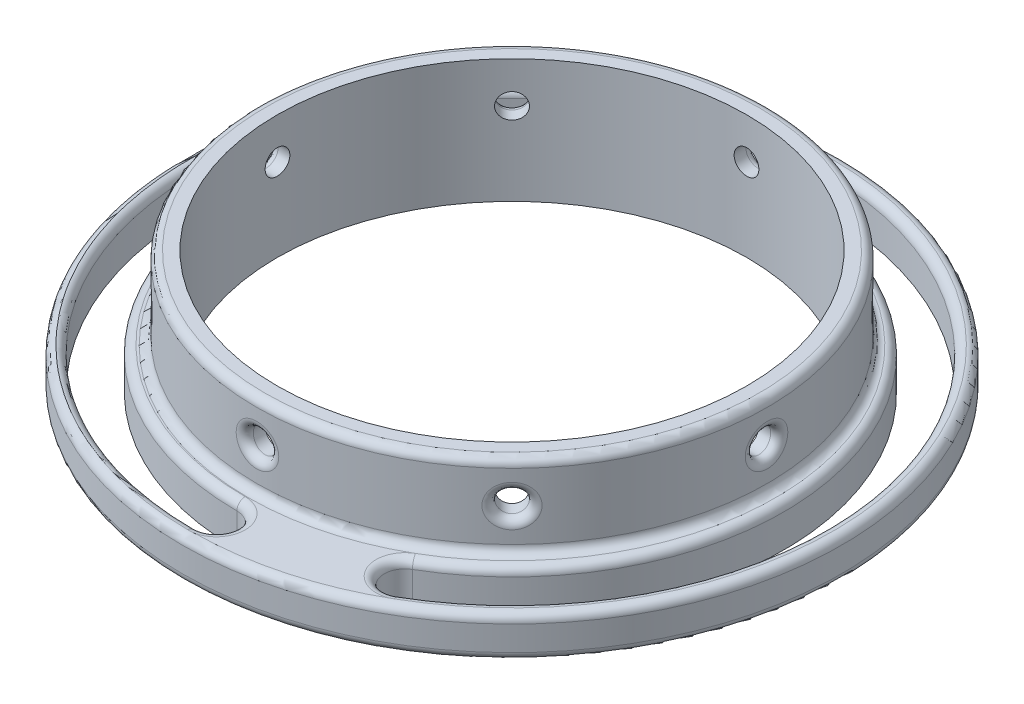
SolidWorks part; units mm, degrees
ref_plane "Front Plane" through (0, 0, 0) normal (0, 0, 1) x (1, 0, 0)
ref_plane "Top Plane" through (0, 0, 0) normal (0, 1, 0) x (1, 0, 0)
ref_plane "Right Plane" through (0, 0, 0) normal (1, 0, 0) x (0, 0, -1)
sketch "Sketch1" plane through (0, 0, 0) normal (0, 1, 0) x (1, 0, 0)
  circle A0 centre (0, 0) radius 40
extrude "Boss-Extrude1" add sketch "Sketch1" along normal blind 5
sketch "Sketch2" plane through (0, 5, 0) normal (0, 1, 0) x (1, 0, 0)
  circle A0 centre (0, 0) radius 31
extrude "Boss-Extrude2" add sketch "Sketch2" along normal blind 10
sketch "Sketch4" plane through (0, 15, 0) normal (0, 1, 0) x (1, 0, 0)
  circle A0 centre (0, 0) radius 28.5
extrude "Cut-Extrude1" cut sketch "Sketch4" against normal up to next
sketch "Sketch5" plane through (0, 0, 0) normal (0, 0, 1) x (1, 0, 0)
  line L0 (0, 18.7787) -> (0, 10.0388) construction
  circle A0 centre (0, 10.0388) radius 1.5
extrude "Cut-Extrude2" cut sketch "Sketch5" against normal up to next
ref_axis "Axis1" through (0, -0.75, 0) along (0, 1, 0)
pattern_circular "CirPattern1" count 8 every 45 about axis through (0, -0.75, 0) along (0, 1, 0) of "Cut-Extrude2"
sketch "Sketch6" plane through (0, 5, 0) normal (0, 1, 0) x (1, 0, 0)
  line L0 (0, 40) -> (0, 31) construction
  circle A0 centre (0, 0) radius 40 construction
  circle A1 centre (0, 0) radius 31 construction
  circle A2 centre (0, 35.5) radius 2.5
extrude "Cut-Extrude3" cut sketch "Sketch6" against normal up to next contours A2
sketch "Sketch7" plane through (0, 5, 0) normal (0, 1, 0) x (1, 0, 0)
  line L0 (0, 38) -> (0, 33) construction
  line L1 (16.5, -28.5788) -> (19, -32.909) construction
  arc A0 (0, 38) -> (0, 33) centre (0, 35.5) cw
  arc A2 (0, 38) -> (19, -32.909) centre (0, 0) cw
  arc A3 (0, 33) -> (16.5, -28.5788) centre (0, 0) cw
  circle A4 centre (0, 35.5) radius 2.5 construction
  arc A5 (19, -32.909) -> (16.5, -28.5788) centre (17.75, -30.7439) cw
  circle M4 centre (0, 35.5) radius 2.5
extrude "Cut-Extrude4" cut sketch "Sketch7" against normal up to next contours A5 A2 A3 M4 region at (35.9252, 5, -9.6261)
sketch "Sketch8" plane through (0, 15, 0) normal (0, 1, 0) x (1, 0, 0)
  line L0 (0, 0) -> (0, -0.6174) construction
  line L3 (0, -0.6174) -> (-11.8221, 43.5033) construction
  line L4 (0, -0.6174) -> (12.5649, -47.5103) construction
ref_plane "Plane1" through (-0.1543, 0, 0.0414) normal (-0.9659, 0, 0.2588) x (0.2588, 0, 0.9659)
mirror "Mirror1" about plane through (-0.1543, 0, 0.0414) normal (-0.9659, 0, 0.2588) of "Cut-Extrude3", "Cut-Extrude4"
fillet "Fillet1" radius 1 20 edges at (0, 0, 40) (0, 15, 31) (-1.4602, 10.3819, -30.9656) (-22.9285, 10.3819, -20.8634) (20.8634, 10.3819, -22.9285) (30.9656, 10.3819, -1.4602) (22.9285, 10.3819, 20.8634) (1.4602, 10.3819, 30.9656) (-20.8634, 10.3819, 22.9285) (-30.9656, 10.3819, 1.4602) (15.5849, 5, 31.9939) (36.7052, 5, -9.8351) (-2.5, 5, -35.5) (31.8756, 5, -8.541) (0, 5, 31) (0, 5, 40) (2.1913, 5, 35.5827) (-32.1842, 5, 8.6237) (-15.8936, 5, -31.9112) (-37.0139, 5, 9.9178)
